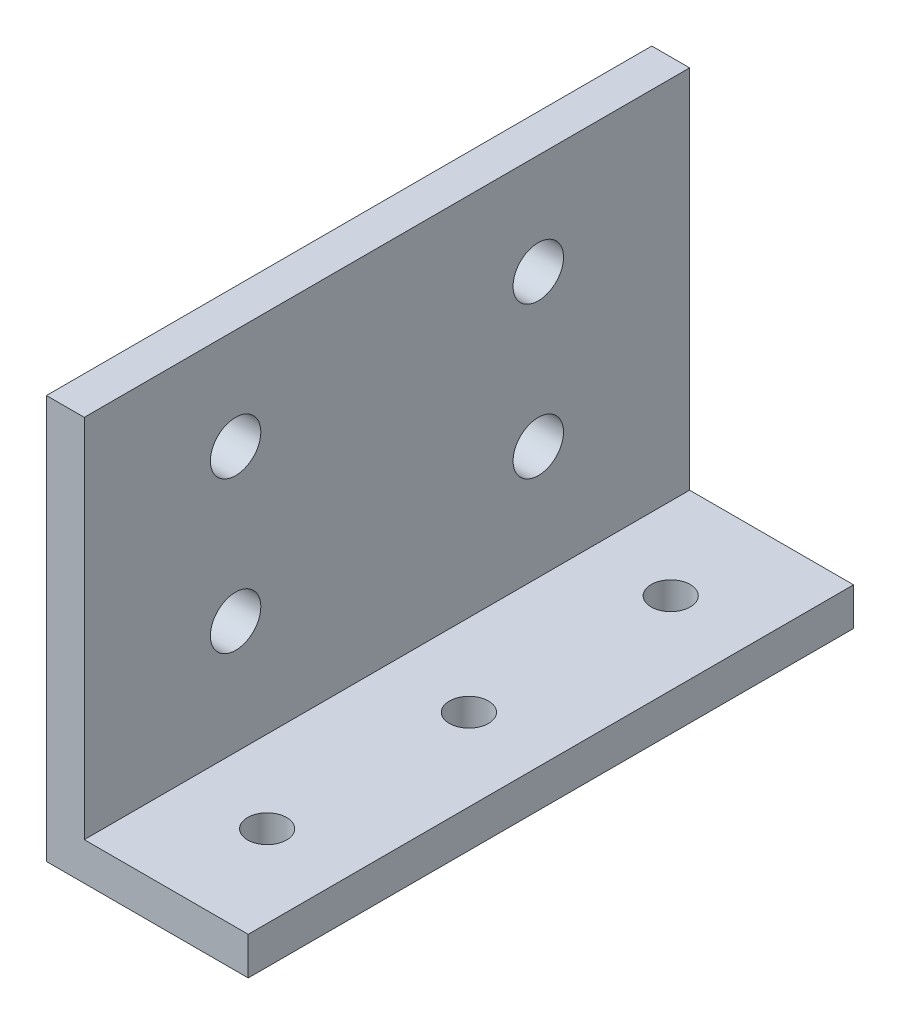
SolidWorks part; units mm, degrees
material "6061 Alloy"
ref_plane "Front Plane" through (0, 0, 0) normal (0, 0, 1) x (1, 0, 0)
ref_plane "Top Plane" through (0, 0, 0) normal (0, 1, 0) x (1, 0, 0)
ref_plane "Right Plane" through (0, 0, 0) normal (1, 0, 0) x (0, 0, -1)
sketch "Sketch1" plane through (0, 0, 0) normal (0, 0, 1) x (1, 0, 0)
  line L0 (0, 0) -> (0, 46.0375)
  line L1 (0, 0) -> (20.6375, 0)
  line L2 (-4.7625, -4.7625) -> (20.6375, -4.7625)
  line L3 (-4.7625, -4.7625) -> (-4.7625, 46.0375)
  line L4 (0, 46.0375) -> (-4.7625, 46.0375)
  line L5 (20.6375, 0) -> (20.6375, -4.7625)
  dimension "D2" = 50.8
  dimension "D3" = 25.4
  dimension "D1" = 4.7625
extrude "Boss-Extrude1" add sketch "Sketch1" along normal blind 76.2
sketch "Sketch2" plane through (0, 0, 0) normal (1, 0, 0) x (0, 0, -1)
  line L0 (-76.2, 46.0375) -> (0, 46.0375) construction
  line L1 (-76.2, 0) -> (-76.2, 46.0375) construction
  circle A0 centre (-57.15, 33.3375) radius 3.175
  circle A1 centre (-19.05, 33.3375) radius 3.175
  circle A3 centre (-19.05, 14.2875) radius 3.175
  circle A5 centre (-57.15, 14.2875) radius 3.175
  dimension "D1" = 6.35
  dimension "D2" = 12.7
  dimension "D3" = 19.05
  dimension "D4" = 2
  dimension "D5" = 2
extrude "Cut-Extrude1" cut sketch "Sketch2" against normal up to next
sketch "Sketch3" plane through (0, 0, 0) normal (0, 1, 0) x (1, 0, 0)
  line L3 (20.6375, -76.2) -> (20.6375, 0) construction
  line L4 (20.6375, -76.2) -> (0, -76.2) construction
  line L5 (10.3187, -63.5) -> (10.3187, -38.1) construction
  point P1 (10.3187, -63.5)
  point P9 (10.3187, -38.1)
  point P11 (10.3187, -12.7)
  dimension "D1" = 10.3187
  dimension "D2" = 12.7
  dimension "D3" = 3
  dimension "D4" = 25.4
hole_wizard "#10 (0.1935) Diameter Hole2" positions "Sketch7" profile "Sketch8" hole size "#10" standard "ANSI Inch" end condition up to next
sketch "Sketch7" plane through (0, 0, 0) normal (0, 1, 0) x (1, 0, 0)
  point P0 (10.3187, -63.5)
  point P3 (10.3187, -38.1)
  point P6 (10.3187, -12.7)
sketch "Sketch8" plane through (10.3187, 0, 63.5) normal (1, 0, 0) x (0, 0, 1)
  line L0 (0, 0) -> (0, 4.7625)
  line L1 (0, 4.7625) -> (2.4574, 4.7625)
  line L2 (2.4574, 4.7625) -> (2.4574, 0)
  line L5 (2.4574, 0) -> (0, 0)
  line L11 (0, -6.35) -> (0, 107.95) construction
  dimension "Thru Hole Dia." = 4.9149
  dimension "Thru Hole Depth" = 4.7625
